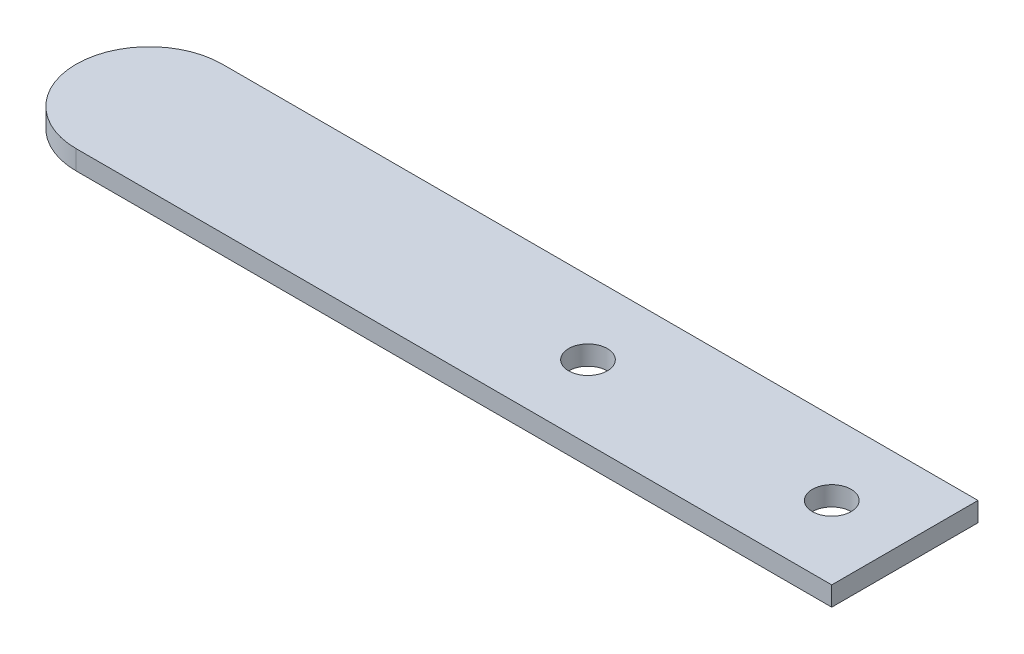
SolidWorks part; units mm, degrees
ref_plane "Front Plane" through (0, 0, 0) normal (0, 0, 1) x (1, 0, 0)
ref_plane "Top Plane" through (0, 0, 0) normal (0, 1, 0) x (1, 0, 0)
ref_plane "Right Plane" through (0, 0, 0) normal (1, 0, 0) x (0, 0, -1)
sketch "Sketch1" plane through (0, 0, 0) normal (0, 1, 0) x (1, 0, 0)
  line L0 (-28, 0) -> (28, 0) construction
  line L1 (34, -6) -> (-28, -6)
  line L2 (34, -6) -> (34, 6)
  line L3 (34, 6) -> (-28, 6)
  line L5 (34, -6) -> (-34, 6) construction
  line L6 (34, 6) -> (-34, -6) construction
  circle A0 centre (-28, 0) radius 1.5875 construction
  circle A1 centre (28, 0) radius 1.5875
  circle A2 centre (-28, 0) radius 5 construction
  circle A3 centre (8, 0) radius 1.5875
  arc A4 (-28, 6) -> (-28, -6) centre (-28, 0) ccw
  point P0 (0, 0)
  point P8 (0, 0)
  dimension "D1" = 3.175
  dimension "D4" = 10
  dimension "D2" = 56
  dimension "D3" = 12
  dimension "D6" = 20
extrude "Boss-Extrude1" add sketch "Sketch1" along normal mid plane 1.5875
